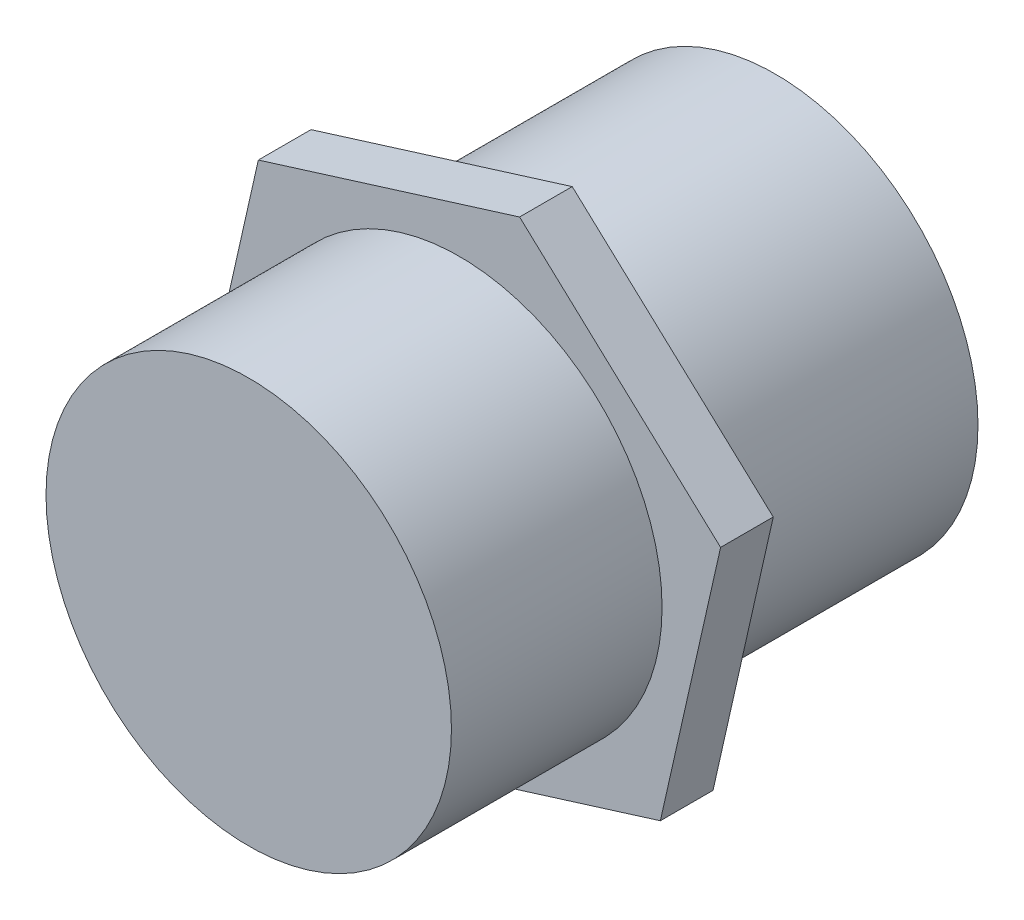
SolidWorks part; units mm, degrees
ref_plane "Front Plane" through (0, 0, 0) normal (0, 0, 1) x (1, 0, 0)
ref_plane "Top Plane" through (0, 0, 0) normal (0, 1, 0) x (1, 0, 0)
ref_plane "Right Plane" through (0, 0, 0) normal (1, 0, 0) x (0, 0, -1)
sketch "Sketch1" plane through (0, 0, 0) normal (0, 0, 1) x (1, 0, 0)
  line L1 (7.6353, -7.0499) -> (9.9231, 3.0874)
  line L2 (9.9231, 3.0874) -> (2.2878, 10.1374)
  line L3 (2.2878, 10.1374) -> (-7.6353, 7.0499)
  line L4 (-7.6353, 7.0499) -> (-9.9231, -3.0874)
  line L5 (-9.9231, -3.0874) -> (-2.2878, -10.1374)
  line L6 (-2.2878, -10.1374) -> (7.6353, -7.0499)
  circle A0 centre (0, 0) radius 7.7
  circle A1 centre (0, 0) radius 9 construction
  dimension "D1" = 15.4
  dimension "D2" = 18
extrude "Boss-Extrude1" add sketch "Sketch1" along normal blind 10 and the other way blind 10 contours A0 region at (0, 0, 0)
extrude "Boss-Extrude2" add sketch "Sketch1<3>" along normal blind 2 separate body contours L5 L6 L1 L2 L3 L4 A0 region at (2.5895, -8.3228, 0)
sketch "Sketch1<3>" plane through (0, 0, 0) normal (0, 0, 1) x (1, 0, 0) same geometry as "Sketch1"
